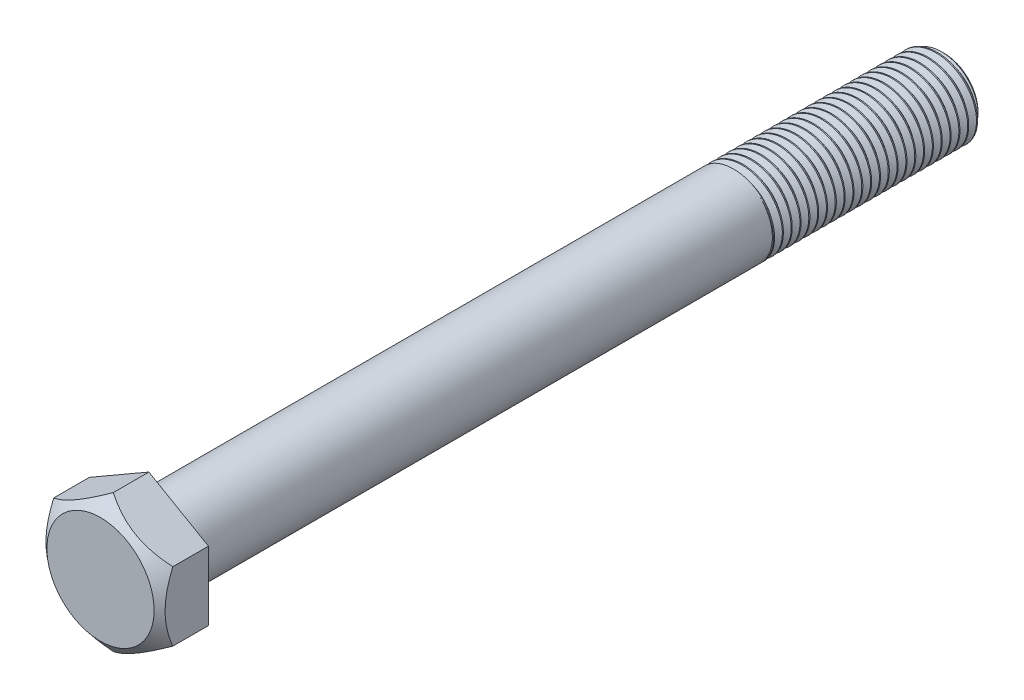
SolidWorks part; units mm, degrees
ref_plane "Front Plane" through (0, 0, 0) normal (0, 0, 1) x (1, 0, 0)
ref_plane "Top Plane" through (0, 0, 0) normal (0, 1, 0) x (1, 0, 0)
ref_plane "Right Plane" through (0, 0, 0) normal (1, 0, 0) x (0, 0, -1)
sketch "Sketch1" plane through (0, 0, 0) normal (1, 0, 0) x (0, 0, -1)
  line L0 (0, 0) -> (95.25, 0) construction
  line L1 (0, 0) -> (-5.9531, 0) construction
  line L2 (95.25, 4.7625) -> (95.25, -4.7625) construction
  line L3 (-5.9531, 7.1437) -> (-5.9531, -7.1438) construction
  line L4 (0, 7.1437) -> (0, -7.1437) construction
  line L5 (95.1839, 4.8771) -> (96.2422, 4.8771) construction
  line L6 (96.2422, 4.8771) -> (95.713, 3.9605) construction
  line L7 (95.713, 3.9605) -> (95.1839, 4.8771) construction
  line L8 (95.2169, 4.8198) -> (96.2091, 4.8198) construction
  line L9 (95.25, 4.7625) -> (96.176, 4.7625) construction
  line L10 (95.6469, 4.0751) -> (95.7792, 4.0751) construction
  line L11 (95.713, 4.0751) -> (95.713, 3.9605) construction
  line L12 (95.713, 4.7625) -> (95.713, 4.8771) construction
  point P6 (95.25, 0)
  point P10 (-5.9531, 0)
  point P12 (0, 0)
  point P18 (91.5458, -4.7625)
  point P25 (95.713, 4.8198)
  point P26 (69.85, 0)
  dimension "Screw Size Decimal Equivalent" = 9.525
  dimension "Head Width" = 14.2875
  dimension "Head Height" = 5.9531
  dimension "Length" = 95.25
  dimension "D1" = 60
  dimension "Thread Pitch" = 1.0583
  dimension "D2" = 0.1323
  dimension "D3" = 3.7042
  dimension "Minimum Thread Length" = 25.4
sketch "Sketch2" plane through (0, 0, 0) normal (1, 0, 0) x (0, 0, -1)
  line L0 (95.25, 0) -> (0, 0)
  line L1 (95.25, 4.7625) -> (95.25, -4.7625) construction
  line L2 (0, 0) -> (0, 4.7625)
  line L3 (0, 7.1437) -> (0, -7.1437) construction
  line L4 (0, 4.7625) -> (94.5092, 4.7625)
  line L5 (94.5092, 4.7625) -> (95.25, 4.0217)
  line L6 (95.25, 4.0217) -> (95.25, 0)
  dimension "D1" = 0.7408
  dimension "D2" = 45
revolve "Revolve1" add sketch "Sketch2" angle 360 about L0
sketch "Sketch3" plane through (0, 0, 0) normal (0, 0, 1) x (1, 0, 0)
  line L1 (0, 8.2489) -> (-7.1437, 4.1244)
  line L2 (-7.1437, 4.1244) -> (-7.1437, -4.1244)
  line L3 (-7.1437, -4.1244) -> (0, -8.2489)
  line L4 (0, -8.2489) -> (7.1437, -4.1244)
  line L5 (7.1437, -4.1244) -> (7.1437, 4.1244)
  line L6 (7.1437, 4.1244) -> (0, 8.2489)
  circle A0 centre (0, 0) radius 7.1437 construction
extrude "Boss-Extrude1" add sketch "Sketch3" along normal up to vertex (5.9531 mm away) up to point (0, 0, 5.9531)
sketch "Sketch4" plane through (0, 0, 5.9531) normal (0, 0, 1) x (1, 0, 0)
  circle A0 centre (0, 0) radius 6.4294
  dimension "D1" = 12.8587
extrude "Cut-Extrude1" cut sketch "Sketch4" against normal through all draft 50 flip side to cut
sketch "Sketch9" plane through (0, 0, 0) normal (0, 0, -1) x (-1, 0, 0)
  circle A0 centre (0, 0) radius 6.7866
  circle A1 centre (0, 0) radius 8.2489
  dimension "D1" = 13.5731
extrude "Cut-Extrude2" cut sketch "Sketch9" against normal blind 0.1488
sketch "Sketch5" plane through (0, 0, 0) normal (1, 0, 0) x (0, 0, -1)
  line L1 (69.85, 4.7625) -> (69.85, -4.7625) construction
  line L4 (95.25, 4.7625) -> (95.25, -4.7625) construction
  point P15 (69.85, 0)
split "Split1" bodies to split 115 resulting bodies 108 109 split by face at (-4.7625, 0, 0)
sketch "Sketch6" plane through (0, 0, 0) normal (1, 0, 0) x (0, 0, -1)
  line L0 (95.2169, 4.8198) -> (96.2091, 4.8198)
  line L1 (96.2091, 4.8198) -> (95.7792, 4.0751)
  line L2 (95.7792, 4.0751) -> (95.6469, 4.0751)
  line L3 (95.6469, 4.0751) -> (95.2169, 4.8198)
sketch "Sketch7" plane through (0, 0, -95.25) normal (0, 0, -1) x (-1, 0, 0)
  circle A0 centre (0, 0) radius 4.7625
curve "Helix/Spiral1" pitch 1.0583 height 26.4583 radius 4.7625 centre (0, 0, -95.25) axis (0, 0, 1) start towards (0, 1, 0)
sweep "Cut-Sweep1" cut profiles "Sketch6" path "Helix/Spiral1" align with end faces yes
combine bodies "Combine1" operation type add bodies to combine 109 110
sketch "Sketch8" plane through (0, 0, 0) normal (1, 0, 0) x (0, 0, -1)
  line L0 (69.85, 0) -> (69.85, 4.7625)
  line L1 (69.85, 4.7625) -> (68.7917, 4.7625)
  line L2 (68.7917, 4.7625) -> (68.7917, 0)
  line L3 (0, 0) -> (95.25, 0) construction
  line L4 (68.7917, 0) -> (69.85, 0)
  line L5 (0, 4.7625) -> (94.5092, 4.7625) construction
  dimension "D1" = 1.0583
revolve "Revolve2" add sketch "Sketch8" angle 360 about L4
equation "\"D2@Sketch1\" = \"Thread Pitch@Sketch1\" / 8"
equation "\"D3@Sketch1\" = \"Thread Pitch@Sketch1\" * 3.5"
equation "\"D1@Sketch2\" = \"Thread Pitch@Sketch1\" * .7"
equation "\"D1@Sketch4\"=\"Head Width@Sketch1\"*.9"
equation "\"D3@Helix/Spiral1\" = \"Minimum Thread Length@Sketch1\" + \"Thread Pitch@Sketch1\""
equation "\"D4@Helix/Spiral1\" = \"Thread Pitch@Sketch1\""
equation "\"D1@Sketch8\" = \"Thread Pitch@Sketch1\""
equation "\"D1@Sketch9\"=\"Head Width@Sketch1\"*.95"
equation "\"D1@Cut-Extrude2\"=\"Head Height@Sketch1\"*.025"
